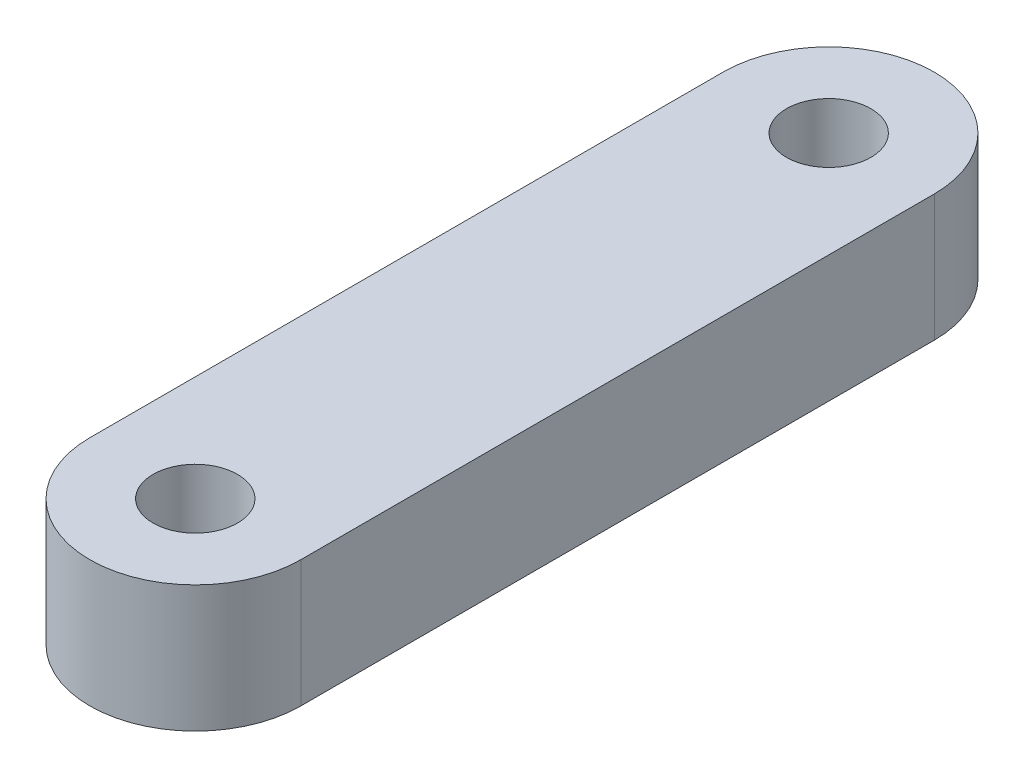
SolidWorks part; units mm, degrees
ref_plane "Alzado" through (0, 0, 0) normal (0, 0, 1) x (1, 0, 0)
ref_plane "Planta" through (0, 0, 0) normal (0, 1, 0) x (1, 0, 0)
ref_plane "Vista lateral" through (0, 0, 0) normal (1, 0, 0) x (0, 0, -1)
sketch "Croquis1" plane through (0, 0, 0) normal (0, 1, 0) x (1, 0, 0)
  line L0 (0, -7.5) -> (0, 7.5) construction
  line L1 (-2.5, -7.5) -> (-2.5, 7.5)
  line L2 (2.5, -7.5) -> (2.5, 7.5)
  arc A0 (-2.5, -7.5) -> (2.5, -7.5) centre (0, -7.5) ccw
  arc A1 (2.5, 7.5) -> (-2.5, 7.5) centre (0, 7.5) ccw
  circle A2 centre (0, 7.5) radius 1
  circle A3 centre (0, -7.5) radius 1
  point P2 (0, 0)
  dimension "D3" = 2
  dimension "D1" = 15
  dimension "D2" = 5
sheet metal parameters "Chapa metálica1" thickness 3 parameters "D1"=0.7366, "Espesor"=3
base flange "Brida base1" sketch "Croquis1" thickness 3 reverse thickness direction no parameters "D1"=0.7366
flat pattern "Chapa desplegada1" [suppressed]
sketch "Líneas de pliegue1" plane through (0, 0, 0) normal (0, 1, 0) x (-1, 0, 0)
sketch3d "Cuadro delimitador1" [suppressed]
  line L0 (-2.5, -12.4995, 0) -> (-2.5, 2.4995, 0) construction
  line L1 (2.5, -12.4995, 0) -> (2.5, 2.4995, 0) construction
  line L2 (-2.5, -12.4995, 0) -> (2.5, -12.4995, 0) construction
  line L3 (-2.5, 2.4995, 0) -> (2.5, 2.4995, 0) construction
